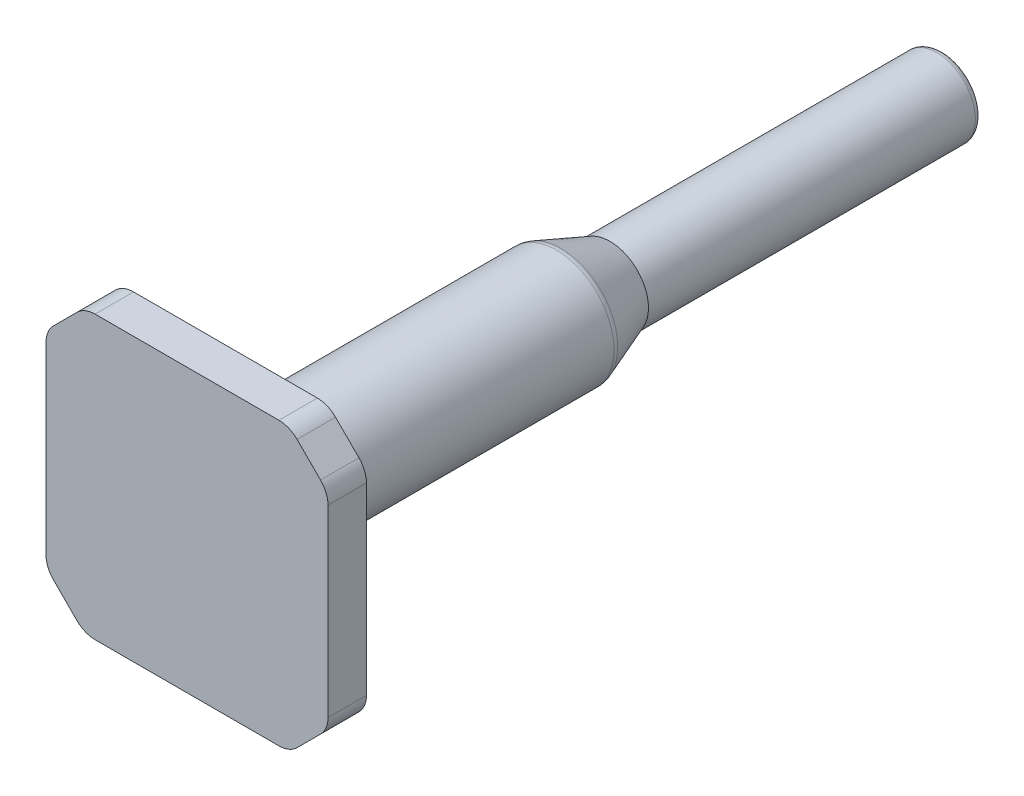
SolidWorks part; units mm, degrees
note: The reader was unsure of these and kept them because the rebuilt part matched: shared geometry of "Sketch1<3>".
material "Alloy Steel"
ref_plane "Front Plane" through (0, 0, 0) normal (0, 0, 1) x (1, 0, 0)
ref_plane "Top Plane" through (0, 0, 0) normal (0, 1, 0) x (1, 0, 0)
ref_plane "Right Plane" through (0, 0, 0) normal (1, 0, 0) x (0, 0, -1)
sketch "Sketch1" plane through (0, 0, 0) normal (0, 0, 1) x (1, 0, 0)
  line L1 (-11, 11) -> (11, 11)
  line L2 (-11, 11) -> (-11, -11)
  line L3 (-11, -11) -> (11, -11)
  line L4 (11, 11) -> (11, -11)
  line L5 (-11, 11) -> (11, -11) construction
  line L6 (-11, -11) -> (11, 11) construction
  circle A0 centre (0, 0) radius 4.5
  point P0 (0, 0)
  dimension "D3" = 9
  dimension "D1" = 22
  dimension "D2" = 22
extrude "Boss-Extrude1" add sketch "Sketch1" along normal blind 3 contours A0 | L4 L1 L2 L3 A0
extrude "Boss-Extrude2" add sketch "Sketch1<3>" against normal blind 30 contours A0
sketch "Sketch1<3>" plane through (0, 0, 0) normal (0, 0, 1) x (1, 0, 0) same geometry as "Sketch1"
sketch "Sketch2" plane through (0, 0, -30) normal (0, 0, -1) x (-1, 0, 0)
  circle A0 centre (0, 0) radius 3
  dimension "D1" = 6
extrude "Boss-Extrude3" add sketch "Sketch2" along normal blind 26
sketch "Sketch3" plane through (0, 0, 0) normal (1, 0, 0) x (0, 0, -1)
  line L4 (30, 3) -> (26, 4.5)
  line L5 (30, 4.5) -> (0, 4.5) construction
  line L6 (30, 0) -> (0, 0) construction
  line L7 (26, 4.5) -> (30, 4.5)
  line L8 (30, 3) -> (30, 4.5)
  dimension "D1" = 4
revolve "Cut-Revolve1" cut sketch "Sketch3" angle 360 about L6
fillet "Fillet1" radius 0.5 1 edges at (4.5, 0, 0)
thread "Thread2" [suppressed] pitch 1 start angle 0, offset 0, length 18, pitch 1, diameter 6
ref_plane "Plane3" through (-3, 0, -30) normal (0, 1, 0) x (1, 0, 0)
sketch "Thread Profile3" plane through (-3, 0, -30) normal (0, 1, 0) x (1, 0, 0)
  line L0 (0, 0) -> (0, 1) construction
  line L11 (0, 0) -> (0, 0.875)
  line L12 (0, 0.875) -> (-0.5413, 0.5625)
  line L13 (-0.5413, 0.5625) -> (-0.5413, 0.3125)
  line L15 (-0.5413, 0.3125) -> (0, 0)
  line L17 (-0.5413, 0.4375) -> (0, 0.4375) construction
  point P2 (0, 0)
  dimension "Pitch" = 1
  dimension "Profile_Angle" = 60
  dimension "Profile_Land" = 0.25
  dimension "Profile_Height" = 0.5413
fillet "Fillet2" [suppressed] radius 1.5
fillet "Fillet3" [suppressed] radius 1.5
fillet "Fillet4" radius 0.5 1 edges at (-3, 0, -56)
fillet "Fillet5" radius 1 1 edges at (0, 4.5, -26)
chamfer "Chamfer2" distance 3 angle 45 4 edges at (11, 11, 1.5) (-11, 11, 1.5) (-11, -11, 1.5) (11, -11, 1.5)
fillet "Fillet7" radius 2 8 edges at (8, -11, 1.5) (11, -8, 1.5) (-11, -8, 1.5) (-8, -11, 1.5) (-11, 8, 1.5) (-8, 11, 1.5) (11, 8, 1.5) (8, 11, 1.5)
